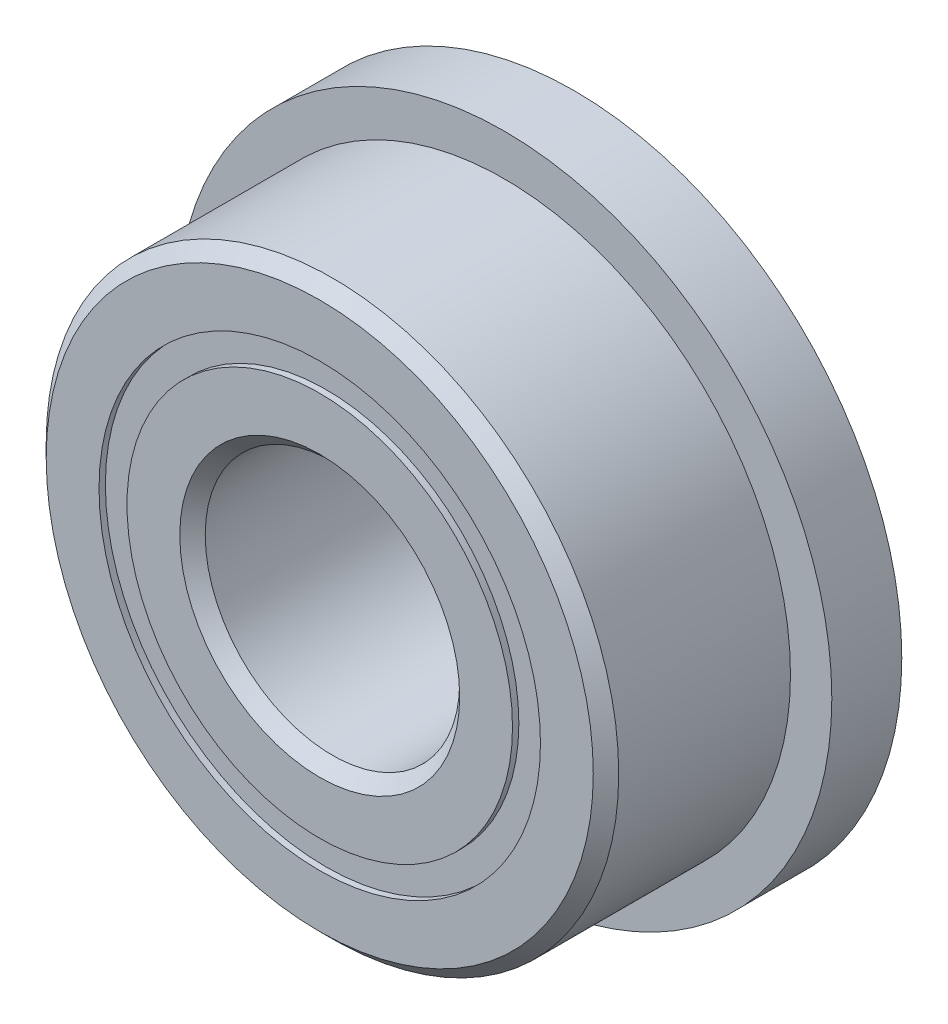
SolidWorks part; units mm, degrees
ref_plane "Front Plane" through (0, 0, 0) normal (0, 0, 1) x (1, 0, 0)
ref_plane "Top Plane" through (0, 0, 0) normal (0, 1, 0) x (1, 0, 0)
ref_plane "Right Plane" through (0, 0, 0) normal (1, 0, 0) x (0, 0, -1)
sketch "Sketch1" plane through (0, 0, 0) normal (1, 0, 0) x (0, 0, -1)
  line L0 (-2, 0) -> (2, 0) construction
  line L1 (0, 4.5) -> (0, -4.5) construction
  line L2 (1.8, 4.5) -> (-1.8, 4.5)
  line L3 (-1.8, 4.5) -> (-2, 4.3)
  line L4 (-2, 4.3) -> (-2, 3.4698)
  line L5 (-2, 3.4698) -> (-0.8889, 3.4698)
  line L6 (2, 3.4698) -> (0.8889, 3.4698)
  line L7 (2, 4.3) -> (2, 3.4698)
  line L8 (1.8, 4.5) -> (2, 4.3)
  line L9 (0, 4.5) -> (0, 3.25) construction
  line L10 (0, 3.25) -> (0, 2) construction
  arc A0 (-0.8889, 3.4698) -> (0.8889, 3.4698) centre (0, 3.25) cw
  point P14 (0, 2)
  dimension "Width" = 4
  dimension "OD" = 9
  dimension "D1" = 45
  dimension "D2" = 0.2
  dimension "Shaft Dia" = 4
  dimension "D3" = 1.7778
  dimension "D4" = 0.2198
revolve "Revolve1" add sketch "Sketch1" angle 360 about L0
sketch "Sketch3" plane through (0, 0, 0) normal (1, 0, 0) x (0, 0, -1)
  line L0 (-2, 3.0302) -> (-0.8889, 3.0302)
  line L1 (0, 4.5) -> (0, -4.5) construction
  line L2 (-2, 4.3) -> (-2, 3.4698) construction
  line L3 (-2, 3.0302) -> (-2, 2.2)
  line L4 (-1.8, 4.5) -> (-2, 4.3) construction
  line L5 (-2, 2.2) -> (-1.8, 2)
  line L6 (-1.8, 2) -> (1.8, 2)
  line L7 (1.8, 4.5) -> (1.8, -4.5) construction
  line L8 (1.8, 2) -> (2, 2.2)
  line L9 (2, -4.3) -> (2, 4.3) construction
  line L10 (2, 2.2) -> (2, 3.0302)
  line L11 (2, 3.0302) -> (0.8889, 3.0302)
  line L13 (1.8, 4.5) -> (2, 4.3) construction
  arc A0 (0.8889, 3.4698) -> (-0.8889, 3.4698) centre (0, 3.25) ccw construction
  arc A1 (0.8889, 3.0302) -> (-0.8889, 3.0302) centre (0, 3.25) cw
revolve "Revolve3" add sketch "Sketch3" angle 360 about L0
sketch "Sketch4" plane through (0, 0, 0) normal (1, 0, 0) x (0, 0, -1)
  line L0 (-0.9157, 3.25) -> (0.9157, 3.25)
  arc A2 (-0.9157, 3.25) -> (0.9157, 3.25) centre (0, 3.25) cw
  arc A3 (0.8889, 3.4698) -> (-0.8889, 3.4698) centre (0, 3.25) ccw construction
revolve "Revolve4" add sketch "Sketch4" angle 360 about L0
ref_axis "Axis1" through (0, 0, -2) along (0, 0, 1)
pattern_circular "CirPattern1" count 12 every 30 about axis through (0, 0, -2) along (0, 0, 1) of bodies 104
sketch "Sketch5" plane through (0, 0, 0) normal (1, 0, 0) x (0, 0, -1)
  line L0 (-2, 3.4698) -> (-0.8889, 3.4698) construction
  line L1 (-1.9, 3.4698) -> (-0.9157, 3.4698)
  line L2 (-1.9, 3.4698) -> (-1.9, 3.0302)
  line L3 (-1.9, 3.0302) -> (-0.9157, 3.0302)
  line L4 (-0.9157, 3.4698) -> (-0.9157, 3.0302)
  line L5 (-2, 3.0302) -> (-0.8889, 3.0302) construction
  line L6 (2, 3.4698) -> (0.8889, 3.4698) construction
  line L7 (1.9, 3.4698) -> (0.9157, 3.4698)
  line L8 (1.9, 3.4698) -> (1.9, 3.0302)
  line L9 (1.9, 3.0302) -> (0.9157, 3.0302)
  line L10 (0.9157, 3.4698) -> (0.9157, 3.0302)
  line L11 (2, 3.0302) -> (0.8889, 3.0302) construction
  line L12 (-1.8, 4.5) -> (-2, 4.3) construction
  point P18 (-1.9, 4.4)
revolve "Revolve5" add sketch "Sketch5" angle 360 about L0
sketch "Sketch6" plane through (0, 0, 0) normal (1, 0, 0) x (0, 0, -1)
  line L0 (2, 0) -> (-2, 0) construction
  line L1 (2, 3.4698) -> (0.9, 3.4698)
  line L2 (2, 3.4698) -> (2, 5.15)
  line L3 (2, 5.15) -> (0.9, 5.15)
  line L4 (0.9, 3.4698) -> (0.9, 5.15)
  dimension "Th" = 1.1
  dimension "Flange OD" = 10.3
revolve "Revolve6" add sketch "Sketch6" angle 360 about L0
equation "\"D2@Sketch1\" = \"Width@Sketch1\"*.05"
equation "\"D3@Sketch1\" = \"Width@Sketch1\"/2.25"
equation "\"D4@Sketch1\" = (((\"OD@Sketch1\"-\"Width@Sketch1\")/2)/3.25)/3.5"
equation "\"D2@CirPattern1\" = 360/\"Balls@CirPattern1\""
